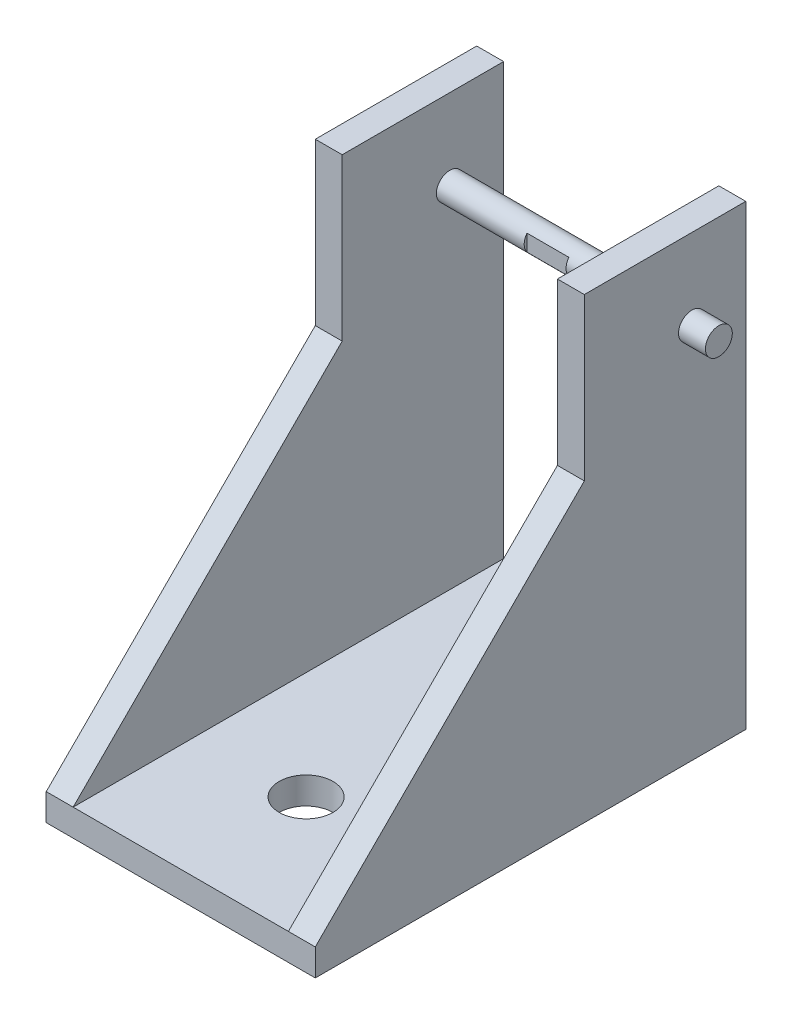
SolidWorks part; units mm, degrees
material "Plain Carbon Steel"
ref_plane "Front Plane" through (0, 0, 0) normal (0, 0, 1) x (1, 0, 0)
ref_plane "Top Plane" through (0, 0, 0) normal (0, 1, 0) x (1, 0, 0)
ref_plane "Right Plane" through (0, 0, 0) normal (1, 0, 0) x (0, 0, -1)
sketch "Sketch2" plane through (0, 0, 0) normal (0, 0, 1) x (1, 0, 0)
  line L1 (0, 0) -> (63.5, 0)
  line L2 (0, 0) -> (0, 6.35)
  line L3 (0, 6.35) -> (63.5, 6.35)
  line L4 (63.5, 0) -> (63.5, 6.35)
  dimension "D1" = 6.35
  dimension "D2" = 63.5
extrude "Base" add sketch "Sketch2" along normal blind 101.6
ref_plane "Plane1" through (31.75, 0, 0) normal (-1, 0, 0) x (0, 0, 1)
sketch "Sketch4" plane through (63.5, 0, 0) normal (1, 0, 0) x (0, 0, -1)
  line L0 (0, 107.95) -> (0, 6.35)
  line L1 (0, 107.95) -> (-38.1, 107.95)
  line L2 (0, 6.35) -> (-101.6, 6.35)
  line L3 (-101.6, 6.35) -> (0, 6.35) construction
  line L4 (-101.6, 6.35) -> (-38.1, 69.85)
  line L5 (-101.6, 0) -> (-101.6, 6.35) construction
  line L6 (-38.1, 107.95) -> (-38.1, 69.85)
  dimension "D1" = 38.1
  dimension "D2" = 45
extrude "Rib" add sketch "Sketch4" against normal blind 6.35
mirror "RibCopy" about plane through (31.75, 0, 0) normal (-1, 0, 0) of "Rib"
sketch "Sketch5" plane through (57.15, 0, 0) normal (-1, 0, 0) x (0, 0, 1)
  line L0 (101.6, 0) -> (0, 0) construction
  line L1 (0, 0) -> (0, 107.95) construction
  circle A0 centre (12.7, 88.9) radius 3.175
  dimension "D1" = 6.35
  dimension "D2" = 88.9
  dimension "D3" = 12.7
extrude "Cut-Extrude1" cut sketch "Sketch5" against normal through all and the other way through all
extrude "Boss-Extrude1" add sketch "Sketch5<2>" along normal blind 63.5 and the other way blind 12.7
sketch "Sketch5<2>" plane through (57.15, 0, 0) normal (-1, 0, 0) x (0, 0, 1) same geometry as "Sketch5"
sketch "Sketch6" plane through (0, 6.35, 0) normal (0, 1, 0) x (-1, 0, 0)
  line L0 (-57.15, 101.6) -> (-57.15, 0) construction
  line L1 (-31.75, 72.0236) -> (-31.75, 32.1145) construction
  circle A0 centre (-31.75, 72.0236) radius 6.35
  circle A1 centre (-31.75, 32.1145) radius 6.35
  dimension "D1" = 12.7
  dimension "D2" = 25.4
extrude "Cut-Extrude2" cut sketch "Sketch6" against normal up to next
sketch "Sketch7" plane through (0, 107.95, 0) normal (0, 1, 0) x (-1, 0, 0)
  line L1 (-27.0783, 15.2106) -> (-36.9616, 15.2106)
  line L2 (-27.0783, 15.2106) -> (-27.0783, 17.3318)
  line L3 (-27.0783, 17.3318) -> (-36.9616, 17.3318)
  line L4 (-36.9616, 15.2106) -> (-36.9616, 17.3318)
extrude "Cut-Extrude3" cut sketch "Sketch7" against normal blind 25.4
